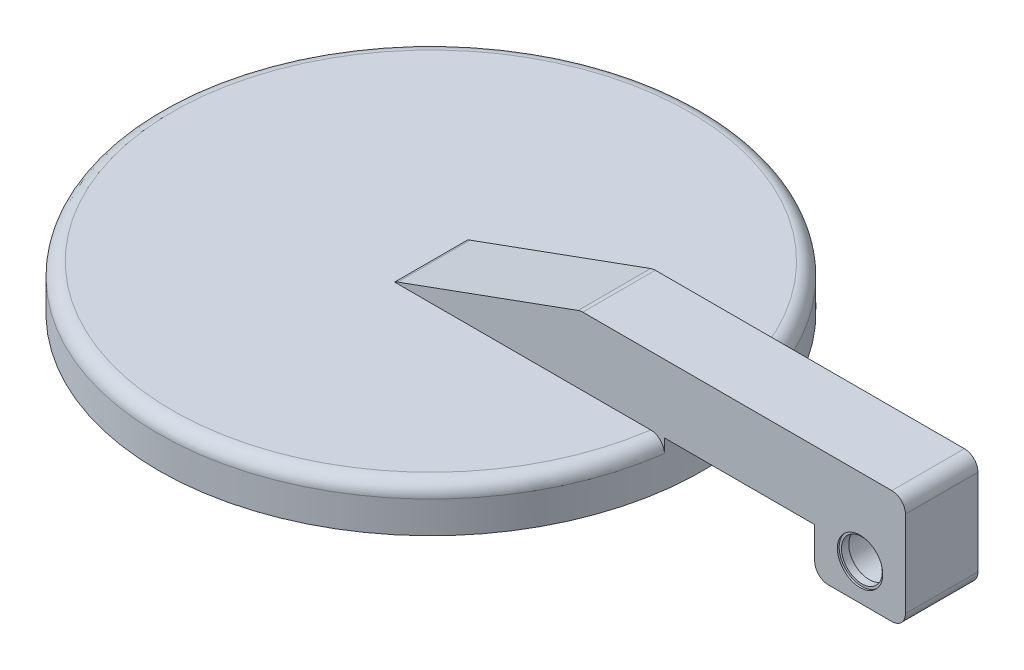
SolidWorks part; units mm, degrees
ref_plane "Front Plane" through (0, 0, 0) normal (0, 0, 1) x (1, 0, 0)
ref_plane "Top Plane" through (0, 0, 0) normal (0, 1, 0) x (1, 0, 0)
ref_plane "Right Plane" through (0, 0, 0) normal (1, 0, 0) x (0, 0, -1)
sketch "Sketch2" plane through (0, 0, 0) normal (0, 0, 1) x (1, 0, 0)
  line L7 (0, 0) -> (30, 0)
  line L8 (0, 0) -> (0, 5)
  line L9 (0, 5) -> (30, 5)
  line L10 (30, 0) -> (30, 5)
  dimension "D1" = 5
  dimension "D2" = 30
revolve "Revolve1" add sketch "Sketch2" angle 360 about L8
sketch "Sketch3" plane through (0, 5, 0) normal (0, 1, 0) x (1, 0, 0)
  line L0 (0, -10) -> (0, 10) construction
  line L1 (0, 10) -> (35, 10)
  line L2 (35, 10) -> (35, 6)
  line L3 (35, 6) -> (0, 6)
  line L4 (0, 10) -> (0, 6)
  line L5 (0, -10) -> (35, -10)
  line L6 (35, -10) -> (35, -6)
  line L7 (35, -6) -> (0, -6)
  line L8 (0, -6) -> (0, -10)
  line L9 (0, 4) -> (0, -4)
  line L10 (0, 4) -> (56.3, 4)
  line L11 (0, -4) -> (56.3, -4)
  line L12 (56.3, -4) -> (56.3, 4)
  point P4 (0, 0)
  point P13 (0, 0)
  circle M1 centre (0, 0) radius 30
  dimension "D1" = 20
  dimension "D2" = 35
  dimension "D3" = 4
  dimension "0.7" = 8
  dimension "D5" = 56.3
extrude "Boss-Extrude1" add sketch "Sketch3" along normal blind 7.5 contours L9 L11 L10 M1 | L11 L12 L10 M1 region at (14.9555, 5, 0) region at (43.1053, 5, 0)
sketch "Sketch4" plane through (0, 0, 0) normal (0, 0, 1) x (1, 0, 0)
  line L5 (35, 8.75) -> (37.8, 8.75) construction
  line L7 (56.3, 8.75) -> (37.8, 8.75) construction
  line L8 (56.3, 12.5) -> (56.3, 5) construction
  line L10 (-0.1339, 5) -> (20.4721, 12.5)
  line L11 (29.7321, 5) -> (-30, 5) construction
  line L12 (0, 12.5) -> (56.3, 12.5) construction
  line L13 (0, 5) -> (29.7321, 5) construction
  line L14 (20.4721, 12.5) -> (0, 12.5)
  line L15 (0, 12.5) -> (-0.1339, 5)
  circle A0 centre (37.8, 8.75) radius 2
  dimension "D3" = 4
  dimension "D1" = 20
  dimension "D2" = 18.5
extrude "Cut-Extrude1" cut sketch "Sketch4" against normal mid plane 30 contours L14 L15 L10
sketch "Sketch6" plane through (0, 5, 0) normal (0, -1, 0) x (1, 0, 0)
  line L6 (56.3, 4) -> (46.3, 4)
  line L7 (56.3, 4) -> (56.3, -4) construction
  line L8 (29.7321, 4) -> (56.3, 4) construction
  line L9 (46.3, 4) -> (46.3, -4)
  line L10 (29.7321, -4) -> (56.3, -4) construction
  line L11 (46.3, -4) -> (56.3, -4)
  line L12 (56.3, -4) -> (56.3, 4)
  dimension "D1" = 10
extrude "Boss-Extrude2" add sketch "Sketch6" along normal blind 5
sketch "Sketch7" plane through (0, 0, 4) normal (0, 0, 1) x (1, 0, 0)
  line L0 (51.3, 4) -> (51.3, 0) construction
  line L2 (56.3, 0) -> (46.3, 0) construction
  circle A0 centre (51.3, 4) radius 2.5
  dimension "D2" = 5
  dimension "D1" = 4
extrude "Cut-Extrude2" cut sketch "Sketch7" against normal blind 10
fillet "Fillet2" radius 1.5 6 edges at (46.3, 0, 0) (56.3, 0, 0) (56.3, 12.5, 0) (20.4721, 12.5, 0) (0, 5.0487, 0) (-30, 5, 0)
sketch "Sketch9" plane through (0, 0, -4) normal (0, 0, -1) x (-1, 0, 0)
  circle A0 centre (-51.3, 4) radius 3
  circle A1 centre (-51.3, 4) radius 4
  dimension "D1" = 6
  dimension "D2" = 8
sketch "Sketch10" plane through (0, 0, 4) normal (0, 0, 1) x (1, 0, 0)
  circle A0 centre (51.3, 4) radius 3
  circle A1 centre (51.3, 4) radius 2.25
  dimension "D1" = 6
  dimension "D2" = 4.5
extrude "Boss-Extrude4" add sketch "Sketch10" along normal blind 0.8 from offset 1 offset against normal yes
